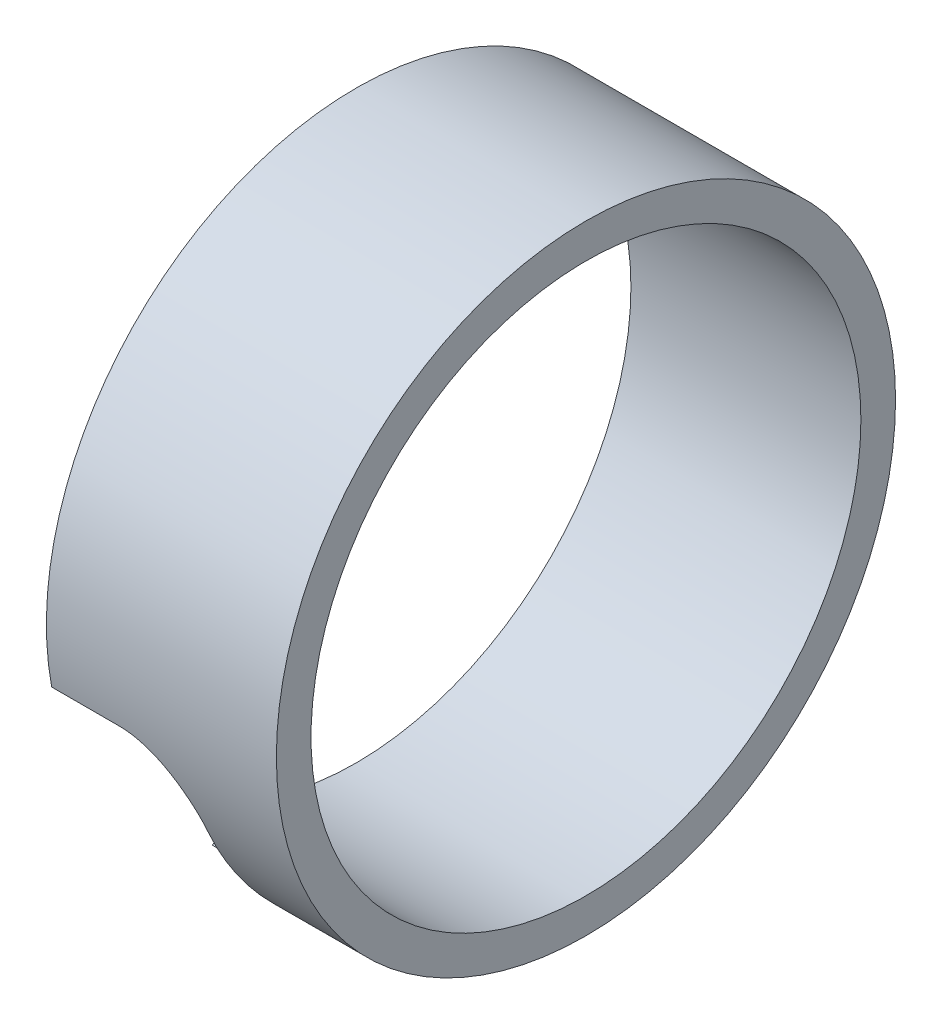
SolidWorks part; units mm, degrees
material "Nylon 6/10"
ref_plane "Front Plane" through (0, 0, 0) normal (0, 0, 1) x (1, 0, 0)
ref_plane "Top Plane" through (0, 0, 0) normal (0, 1, 0) x (1, 0, 0)
ref_plane "Right Plane" through (0, 0, 0) normal (1, 0, 0) x (0, 0, -1)
sketch "Sketch1" plane through (0, 0, 0) normal (0, 0, 1) x (1, 0, 0)
  line L0 (-25.4, 7.5) -> (-42.315, 7.5) construction
  line L1 (-39.013, 8.7312) -> (-32.527, 8.7312)
  line L2 (-39.013, 8.7312) -> (-39.013, 7.754)
  line L3 (-39.013, 7.754) -> (-32.527, 7.754)
  line L4 (-32.527, 8.7312) -> (-32.527, 7.754)
  line L5 (-39.14, -5.0513) -> (-39.14, 1.0832) construction
  line L6 (-32.4, 15.2446) -> (-32.4, -15.2446) construction
  line L7 (0, 0) -> (-47.1489, 0) construction
  dimension "D1" = 0.254
  dimension "D2" = 0.127
  dimension "D3" = 0.127
  dimension "D4" = 17.4625
revolve "Revolve1" add sketch "Sketch1" angle 360 about L7
ref_plane "Plane1" through (0, 0, 0) normal (0, -0.5944, 0.8041) x (1, 0, 0)
sketch "Sketch3" plane through (0, 0, 0) normal (0, -0.5944, 0.8041) x (1, 0, 0)
  line L0 (-39.013, 3.81) -> (-39.013, -3.81)
  line L1 (-39.013, 7.754) -> (-39.013, -7.754) construction
  line L2 (-39.013, -3.81) -> (-37.108, -3.81)
  line L3 (-35.203, -1.905) -> (-35.203, 1.905)
  line L4 (-37.108, 3.81) -> (-39.013, 3.81)
  line L5 (-39.013, 8.7313) -> (-39.013, -8.7312) construction
  line L6 (-39.013, 8.7313) -> (-39.013, -8.7312) construction
  line L7 (-35.203, 0) -> (-39.013, 0) construction
  arc A0 (-37.108, -3.81) -> (-35.203, -1.905) centre (-37.108, -1.905) ccw
  arc A1 (-35.203, 1.905) -> (-37.108, 3.81) centre (-37.108, 1.905) ccw
  dimension "D1" = 7.62
  dimension "D2" = 3.81
extrude "Cut-Extrude1" cut sketch "Sketch3" along normal up to next
